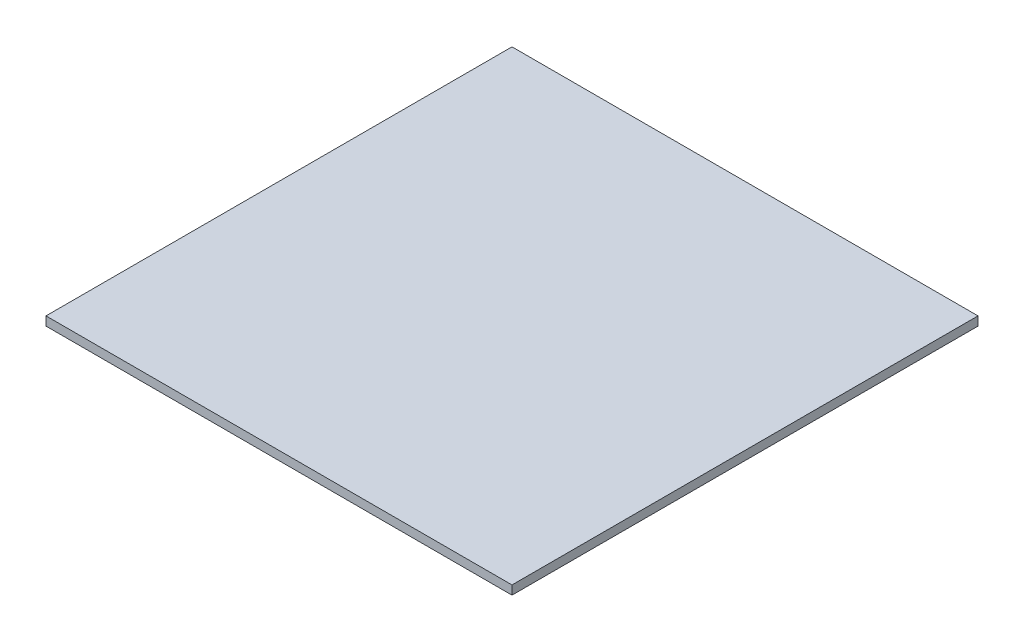
SolidWorks part; units mm, degrees
ref_plane "Спереди" through (0, 0, 0) normal (0, 0, 1) x (1, 0, 0)
ref_plane "Сверху" through (0, 0, 0) normal (0, 1, 0) x (1, 0, 0)
ref_plane "Справа" through (0, 0, 0) normal (1, 0, 0) x (0, 0, -1)
sketch "Эскиз1" plane through (0, 0, 0) normal (0, 1, 0) x (1, 0, 0)
  line L1 (-150, -150) -> (150, -150) construction
  line L2 (-150, -150) -> (-150, 150) construction
  line L3 (-150, 150) -> (150, 150) construction
  line L4 (150, -150) -> (150, 150) construction
  line L5 (-150, -150) -> (150, 150) construction
  line L6 (-150, 150) -> (150, -150) construction
  line L7 (-105, -105) -> (105, -105)
  line L8 (-105, -105) -> (-105, 105)
  line L9 (-105, 105) -> (105, 105)
  line L10 (105, -105) -> (105, 105)
  line L11 (-105, -105) -> (105, 105) construction
  line L12 (-105, 105) -> (105, -105) construction
  circle A0 centre (0, 0) radius 150 construction
  point P0 (0, 0)
  point P6 (0, 0)
  dimension "D1" = 300
  dimension "D2" = 210
extrude "Бобышка-Вытянуть1" add sketch "Эскиз1" along normal blind 4 contours L8 L9 L10 L7
